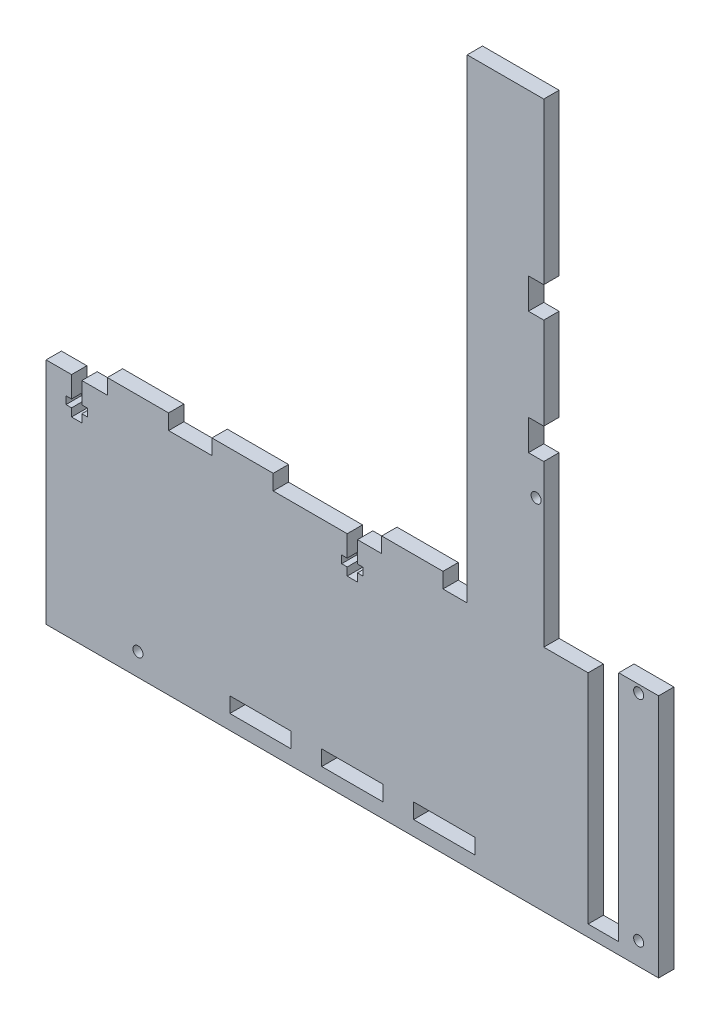
SolidWorks part; units mm, degrees
ref_plane "Front Plane" through (0, 0, 0) normal (0, 0, 1) x (1, 0, 0)
ref_plane "Top Plane" through (0, 0, 0) normal (0, 1, 0) x (1, 0, 0)
ref_plane "Right Plane" through (0, 0, 0) normal (1, 0, 0) x (0, 0, -1)
sketch "Sketch1" plane through (0, 0, 0) normal (0, 1, 0) x (1, 0, 0)
  line L0 (0, 15.4483) -> (0, 24.666) construction
  line L1 (-143.9938, 3.175) -> (110.0062, 3.175)
  line L2 (-143.9938, 3.175) -> (-143.9938, -3.175)
  line L3 (-143.9938, -3.175) -> (110.0062, -3.175)
  line L4 (110.0062, 3.175) -> (110.0062, -3.175)
  line L5 (8.1935, 0) -> (24.922, 0) construction
  dimension "D2" = 6.35
extrude "Base Extrusion" add sketch "Sketch1" along normal up to surface (94.9946 mm away)
sketch "Sketch4" plane through (0, 0, 3.175) normal (0, 0, 1) x (1, 0, 0)
  line L0 (110.0062, 12.4446) -> (-143.9938, 12.4446) construction
  line L1 (-67.7938, 12.4446) -> (-42.3938, 12.4446)
  line L2 (-67.7938, 12.4446) -> (-67.7938, 6.0946)
  line L3 (-67.7938, 6.0946) -> (-42.3938, 6.0946)
  line L4 (-42.3938, 12.4446) -> (-42.3938, 6.0946)
  line L5 (-29.6938, 12.4446) -> (-4.2938, 12.4446)
  line L6 (-29.6938, 12.4446) -> (-29.6938, 6.0946)
  line L7 (-29.6938, 6.0946) -> (-4.2938, 6.0946)
  line L8 (-4.2938, 12.4446) -> (-4.2938, 6.0946)
  line L9 (8.4062, 12.4446) -> (33.8062, 12.4446)
  line L10 (8.4062, 12.4446) -> (8.4062, 6.0946)
  line L11 (8.4062, 6.0946) -> (33.8062, 6.0946)
  line L12 (33.8062, 12.4446) -> (33.8062, 6.0946)
  line L13 (364.0062, 6.0946) -> (110.0062, 6.0946) construction
  line L14 (110.0062, 12.4446) -> (-143.9938, 12.4446) construction
  line L15 (364.0062, 6.0946) -> (110.0062, 6.0946) construction
  line L17 (-16.9938, 40.6411) -> (-16.9938, -10.2729) construction
  line L18 (-143.9938, 94.9946) -> (-143.9938, 0) construction
  line L19 (110.0062, 94.9946) -> (110.0062, 0) construction
  dimension "D1" = 25.4
  dimension "D2" = 25.4
  dimension "D3" = 25.4
  dimension "D5" = 12.7
  dimension "D6" = 12.7
extrude "Tab Holes to Chassis Base" cut sketch "Sketch4" against normal through all
sketch "Sketch5" plane through (0, 0, 3.175) normal (0, 0, 1) x (1, 0, 0)
  line L0 (-16.9938, 67.1576) -> (-16.9938, 113.4981) construction
  line L1 (-143.9938, 94.9946) -> (-143.9938, 0) construction
  line L2 (110.0062, 94.9946) -> (110.0062, 0) construction
  line L3 (110.0062, 94.9946) -> (-143.9938, 94.9946) construction
  line B0 (-14.8602, 94.9946) -> (-19.1274, 94.9946)
  line B1 (-19.1274, 83.0566) -> (-21.4388, 83.0566)
  line B2 (-21.4388, 83.0566) -> (-21.4388, 86.2316)
  line B3 (-21.4388, 86.2316) -> (-19.1274, 86.2316)
  line B4 (-19.1274, 86.2316) -> (-19.1274, 94.9946)
  line B5 (-19.1274, 83.0566) -> (-19.1274, 79.7546)
  line B6 (-19.1274, 79.7546) -> (-14.8602, 79.7546)
  line B7 (-14.8602, 83.0566) -> (-14.8602, 79.7546)
  line B8 (-14.8602, 86.2316) -> (-14.8602, 94.9946)
  line B9 (-12.5488, 86.2316) -> (-14.8602, 86.2316)
  line B10 (-12.5488, 83.0566) -> (-12.5488, 86.2316)
  line B11 (-14.8602, 83.0566) -> (-12.5488, 83.0566)
sketch_block_instance "TSlot-1"
sketch_block "TSlot" parameters "D1"=3.302, "D2"=3.175
extrude "T Slot Center" cut sketch "Sketch5" against normal through all
sketch "Sketch6" plane through (0, 0, 3.175) normal (0, 0, 1) x (1, 0, 0)
  line L0 (110.0062, 94.9946) -> (-14.8602, 94.9946) construction
  line L1 (62.3812, 94.9946) -> (30.6312, 94.9946)
  line L2 (62.3812, 94.9946) -> (62.3812, 291.8446)
  line L3 (62.3812, 291.8446) -> (30.6312, 291.8446)
  line L4 (30.6312, 94.9946) -> (30.6312, 291.8446)
  line L5 (62.3812, 12.4446) -> (62.3812, 144.931) construction
  line L6 (56.0312, 291.8446) -> (62.3812, 291.8446) construction
  dimension "D1" = 31.75
extrude "Arm Support" add sketch "Sketch6" against normal up to surface (6.35 mm away) up to face at (-16.9938, 76.04, -3.175)
sketch "Sketch8" plane through (0, 94.9946, 0) normal (0, 1, 0) x (1, 0, 0)
  line L0 (80.775, -3.175) -> (80.775, 3.175)
  line L1 (80.775, -3.175) -> (93.475, -3.175)
  line L2 (80.775, 3.175) -> (93.475, 3.175)
  line L3 (93.475, -3.175) -> (93.475, 3.175)
  line L4 (110.0062, -3.175) -> (62.3812, -3.175) construction
  line L5 (62.3812, 3.175) -> (110.0062, 3.175) construction
  line L6 (87.125, -7.9885) -> (87.125, 24.6597) construction
extrude "Arm Clearance" cut sketch "Sketch8" against normal offset from surface (90.2321 mm away) 4.7625 up to face at (-16.9938, 0, 0)
sketch "Sketch9" plane through (0, 0, 3.175) normal (0, 0, 1) x (1, 0, 0)
  line L0 (96.3524, 9.2439) -> (106.7258, 9.2439) construction
  line L3 (101.7406, 25.5557) -> (101.7406, 3.267) construction
  line L4 (93.475, 4.7625) -> (93.475, 94.9946) construction
  line L5 (110.0062, 94.9946) -> (110.0062, 0) construction
  circle A0 centre (101.7406, 9.2439) radius 2.0955
  dimension "D1" = 4.191
extrude "Base Mounting Hole 1" cut sketch "Sketch9" against normal through all
sketch "Sketch10" plane through (0, 0, 3.175) normal (0, 0, 1) x (1, 0, 0)
  line L0 (-78.6997, 9.2696) -> (-124.1873, 9.2696) construction
  line L5 (-42.3938, 12.4446) -> (-67.7938, 12.4446) construction
  line L6 (-67.7938, 6.0946) -> (-42.3938, 6.0946) construction
  line L7 (-105.8938, 38.7875) -> (-105.8938, -6.1881) construction
  line L8 (-143.9938, 94.9946) -> (-143.9938, 0) construction
  line L9 (-67.7938, 12.4446) -> (-67.7938, 6.0946) construction
  circle A0 centre (-105.8938, 9.2696) radius 2.0955
  circle A1 centre (101.7406, 9.2439) radius 2.0955 construction
extrude "Base Mounting Hole 2" cut sketch "Sketch10" against normal through all
sketch "Sketch11" plane through (0, 0, 3.175) normal (0, 0, 1) x (1, 0, 0)
  line L0 (39.2564, 147.0646) -> (78.7704, 147.0646) construction
  line L1 (62.3812, 149.1982) -> (56.0312, 149.1982) construction
  line L2 (56.0312, 144.931) -> (62.3812, 144.931) construction
  line L3 (59.2062, 189.1979) -> (59.2062, 134.4872) construction
  line L4 (62.3812, 291.8446) -> (62.3812, 94.9946) construction
  line L5 (56.0312, 149.1982) -> (56.0312, 161.6696) construction
  circle A0 centre (59.2062, 147.0646) radius 2.0955
  circle A1 centre (101.7406, 9.2439) radius 2.0955 construction
extrude "Arm Support Mounting Hole" cut sketch "Sketch11" against normal through all
sketch "Sketch12" plane through (0, 0, 3.175) normal (0, 0, 1) x (1, 0, 0)
  line L0 (62.3812, 94.9946) -> (62.3812, 291.8446) construction
  line L1 (56.0312, 225.1696) -> (62.3812, 225.1696)
  line L2 (56.0312, 225.1696) -> (56.0312, 212.4696)
  line L3 (56.0312, 212.4696) -> (62.3812, 212.4696)
  line L4 (62.3812, 225.1696) -> (62.3812, 212.4696)
  line L5 (56.0312, 174.3696) -> (62.3812, 174.3696)
  line L6 (56.0312, 174.3696) -> (56.0312, 161.6696)
  line L7 (56.0312, 161.6696) -> (62.3812, 161.6696)
  line L8 (62.3812, 174.3696) -> (62.3812, 161.6696)
  line L9 (56.0312, 161.6696) -> (56.0312, 174.3696) construction
  line L10 (56.0312, 174.3696) -> (62.3812, 174.3696) construction
  line L11 (62.3812, 161.6696) -> (56.0312, 161.6696) construction
  line L12 (56.0312, 212.4696) -> (56.0312, 225.1696) construction
  line L13 (56.0312, 225.1696) -> (62.3812, 225.1696) construction
  line L14 (62.3812, 212.4696) -> (56.0312, 212.4696) construction
extrude "Arm Support Tab Slots" cut sketch "Sketch12" against normal through all
sketch "Sketch13" plane through (0, 94.9946, 0) normal (0, 1, 0) x (1, 0, 0)
  line L0 (-143.9938, 3.175) -> (-19.1274, 3.175) construction
  line L1 (93.475, 3.175) -> (110.0062, 3.175)
  line L2 (93.475, 3.175) -> (93.475, -3.175)
  line L3 (93.475, -3.175) -> (110.0062, -3.175)
  line L4 (110.0062, 3.175) -> (110.0062, -3.175)
  line L5 (-118.5938, 3.175) -> (-93.1938, 3.175)
  line L6 (-118.5938, 3.175) -> (-118.5938, -3.175)
  line L7 (-118.5938, -3.175) -> (-93.1938, -3.175)
  line L8 (-93.1938, 3.175) -> (-93.1938, -3.175)
  line L9 (-19.1274, -3.175) -> (-143.9938, -3.175) construction
  line L10 (-14.8602, 3.175) -> (30.6312, 3.175) construction
  line L11 (-4.8145, 3.175) -> (20.5855, 3.175)
  line L12 (-4.8145, 3.175) -> (-4.8145, -3.175)
  line L13 (-4.8145, -3.175) -> (20.5855, -3.175)
  line L14 (20.5855, 3.175) -> (20.5855, -3.175)
  line L15 (30.6312, -3.175) -> (-14.8602, -3.175) construction
  line L16 (7.8855, 19.4293) -> (7.8855, -15.2554) construction
  line L17 (-75.2106, 3.175) -> (-49.8106, 3.175)
  line L18 (-75.2106, 3.175) -> (-75.2106, -3.175)
  line L19 (-75.2106, -3.175) -> (-49.8106, -3.175)
  line L20 (-49.8106, 3.175) -> (-49.8106, -3.175)
  line L21 (-14.8602, 3.175) -> (-14.8602, -3.175) construction
  line L22 (30.6312, 3.175) -> (30.6312, -3.175) construction
  line L23 (-105.8938, 22.3632) -> (-105.8938, -15.2554) construction
  line L28 (-62.5106, 22.3632) -> (-62.5106, -21.1411) construction
  line L29 (-19.1274, 3.175) -> (-19.1274, -3.175) construction
  dimension "D1" = 25.4
extrude "Top Plate Tab" add sketch "Sketch13" along normal blind 6.35
sketch "Sketch14" plane through (0, 0, 3.175) normal (0, 0, 1) x (1, 0, 0)
  line L0 (-131.2938, 71.8951) -> (-131.2938, 106.4008) construction
  line L1 (-118.5938, 94.9946) -> (-143.9938, 94.9946) construction
  line L2 (-143.9938, 94.9946) -> (-143.9938, 0) construction
  line L3 (-118.5938, 101.3446) -> (-118.5938, 94.9946) construction
  line B0 (-129.1602, 94.9946) -> (-133.4274, 94.9946)
  line B1 (-133.4274, 83.0566) -> (-135.7388, 83.0566)
  line B2 (-135.7388, 83.0566) -> (-135.7388, 86.2316)
  line B3 (-135.7388, 86.2316) -> (-133.4274, 86.2316)
  line B4 (-133.4274, 86.2316) -> (-133.4274, 94.9946)
  line B5 (-133.4274, 83.0566) -> (-133.4274, 79.7546)
  line B6 (-133.4274, 79.7546) -> (-129.1602, 79.7546)
  line B7 (-129.1602, 83.0566) -> (-129.1602, 79.7546)
  line B8 (-129.1602, 86.2316) -> (-129.1602, 94.9946)
  line B9 (-126.8488, 86.2316) -> (-129.1602, 86.2316)
  line B10 (-126.8488, 83.0566) -> (-126.8488, 86.2316)
  line B11 (-129.1602, 83.0566) -> (-126.8488, 83.0566)
sketch_block_instance "TSlot-3"
extrude "T Slot Top Corner" cut sketch "Sketch14" against normal through all
sketch "Sketch15" plane through (0, 0, 3.175) normal (0, 0, 1) x (1, 0, 0)
  line L0 (101.7406, 99.797) -> (101.7406, 89.693) construction
  line L1 (93.475, 4.7625) -> (93.475, 101.3446) construction
  line L2 (110.0062, 101.3446) -> (110.0062, 0) construction
  line L3 (95.644, 98.1696) -> (106.8624, 98.1696) construction
  line L7 (62.3812, 94.9946) -> (80.775, 94.9946) construction
  line L8 (-4.8145, 101.3446) -> (20.5855, 101.3446) construction
  circle A0 centre (101.7406, 98.1696) radius 2.0955
  dimension "D1" = 4.191
extrude "Cut-Extrude8" cut sketch "Sketch15" against normal through all
